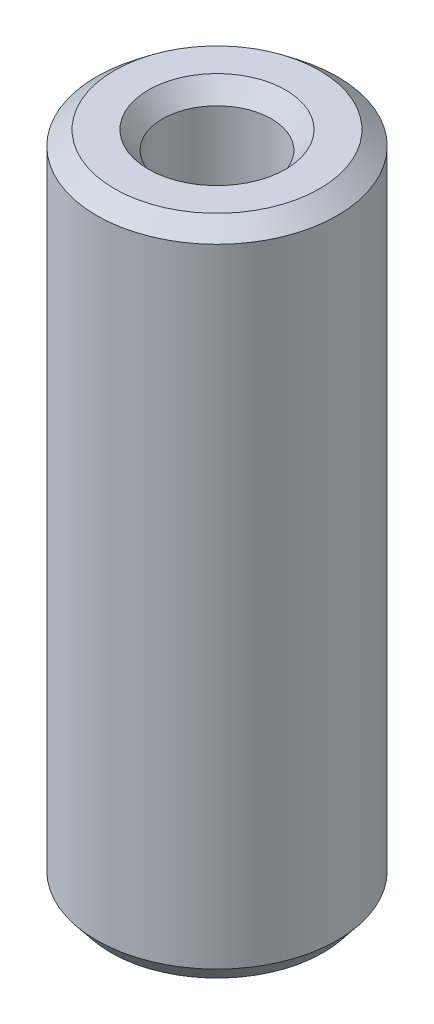
SolidWorks part; units mm, degrees
ref_plane "Front Plane" through (0, 0, 0) normal (0, 0, 1) x (1, 0, 0)
ref_plane "Top Plane" through (0, 0, 0) normal (0, 1, 0) x (1, 0, 0)
ref_plane "Right Plane" through (0, 0, 0) normal (1, 0, 0) x (0, 0, -1)
sketch "Sketch1" plane through (0, 0, 0) normal (0, 1, 0) x (1, 0, 0)
  circle A0 centre (0, 0) radius 17.5
  dimension "SLEEVE_OD" = 35
extrude "Boss-Extrude1" add sketch "Sketch1" along normal blind 95.9355
sketch "Sketch2" plane through (0, 0, 0) normal (0, 1, 0) x (1, 0, 0)
  circle A0 centre (0, 0) radius 7.9093
  dimension "BORE_D" = 15.8186
extrude "Cut-Extrude1" cut sketch "Sketch2" along normal through all
chamfer "Chamfer1" distance 2.0737 angle 51.357 4 edges at (0, 95.9355, 7.9093) (0, 0, 7.9093) (0, 0, 17.5) (0, 95.9355, 17.5) first distance on face at (0, 95.9355, 7.9093) first distance on face at (0, 0, 7.9093) first distance on face at (0, 95.9355, 17.5)
